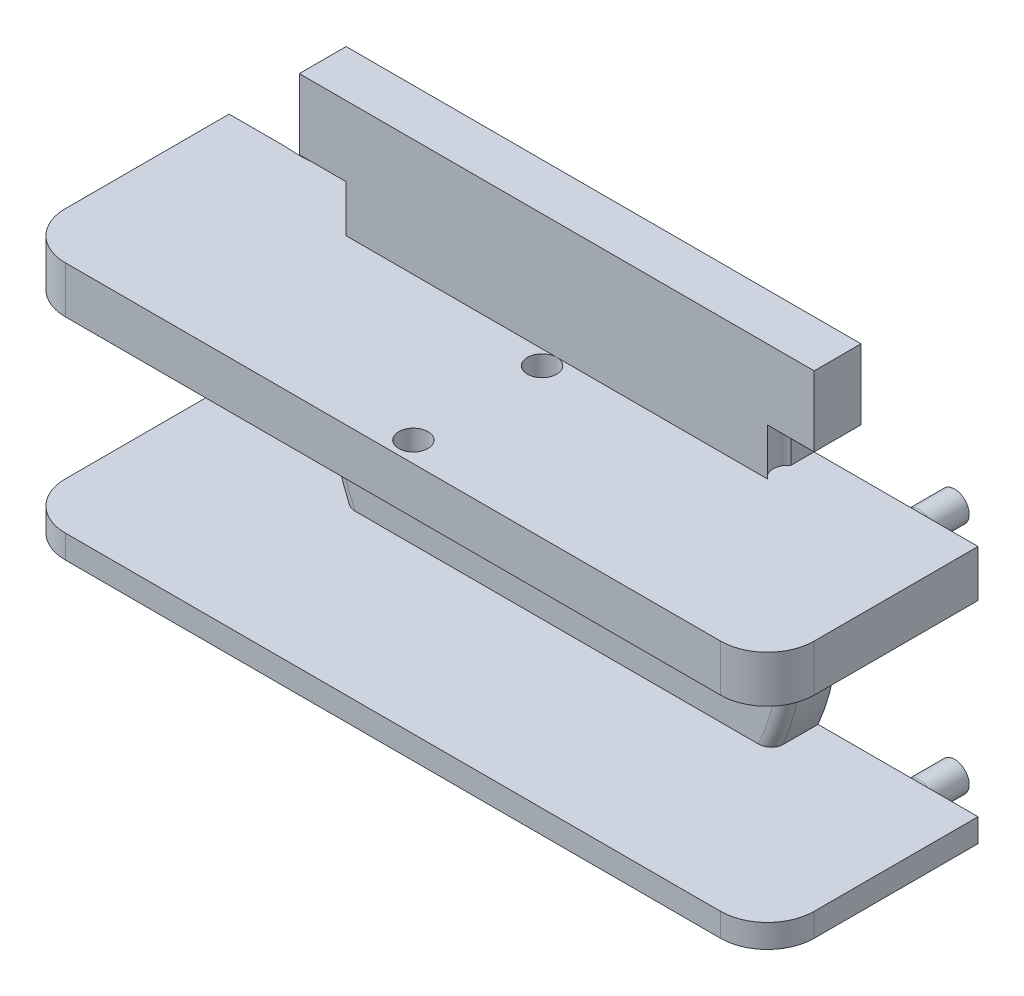
SolidWorks part; units mm, degrees
material "UNOBTANIUM"
ref_plane "Top Plane" through (0, 0, 0) normal (0, 0, 1) x (1, 0, 0)
ref_plane "Right Plane" through (0, 0, 0) normal (0, 1, 0) x (1, 0, 0)
ref_plane "Front Plane" through (0, 0, 0) normal (1, 0, 0) x (0, 0, -1)
ref_axis "x-axis" through (-17.6, 0, 0) along (1, 0, 0)
ref_axis "y-axis" through (0, -9.7375, 0) along (0, 1, 0)
ref_axis "z-axis" through (0, 0, 8.775) along (0, 0, -1)
sketch "Sketch1" plane through (0, 0, 0) normal (0, 0, 1) x (1, 0, 0)
  line L0 (-11, 6) -> (-11, 11)
  line L1 (-11, -6) -> (11, -6)
  line L2 (-11, -6) -> (-11, 6)
  line L3 (-11, 6) -> (11, 6) construction
  line L4 (11, -6) -> (11, 6)
  line L5 (-11, -6) -> (11, 6) construction
  line L6 (-11, 6) -> (11, -6) construction
  line L7 (-11, 11) -> (11, 11)
  line L8 (11, 11) -> (11, 6)
  circle A0 centre (0, 0) radius 9.25 construction
  point P0 (0, 0)
  dimension "D1" = 18.5
  dimension "D2" = 22
  dimension "D3" = 12
  dimension "D4" = 5
extrude "Boss-Extrude1" add sketch "Sketch1" along normal blind 2
sketch "Sketch2" plane through (0, 0, 2) normal (0, 0, -1) x (-1, 0, 0)
  circle A0 centre (0, 0) radius 1.575
  dimension "D1" = 3.15
extrude "Boss-Extrude2" add sketch "Sketch2" along normal blind 4 separate body
sketch "Sketch3" plane through (0, 0, 0) normal (0, 0, -1) x (-1, 0, 0)
  line L0 (11, -6) -> (-11, 6) construction
  circle A0 centre (0, 0) radius 1.8
  dimension "D1" = 3.6
extrude "Boss-Extrude3" add sketch "Sketch3" along normal blind 1
sketch "Sketch4" plane through (0, 0, 0) normal (0, 0, -1) x (-1, 0, 0)
  line L0 (11, -6) -> (-11, -6) construction
  line L1 (11, 11) -> (9, 11)
  line L2 (11, 11) -> (11, -6)
  line L3 (11, -6) -> (9, -6)
  line L4 (9, 11) -> (9, -6)
  line L5 (0, -6) -> (0, 11) construction
  line L7 (-9, 11) -> (-9, -6)
  line L8 (-11, -6) -> (-9, -6)
  line L9 (-11, 11) -> (-11, -6)
  line L10 (-11, 11) -> (-9, 11)
  line L11 (11, 11) -> (-11, 11) construction
  dimension "D1" = 2
extrude "Boss-Extrude4" add sketch "Sketch4" along normal blind 0.001
sketch "Sketch5" plane through (0, 0, 0) normal (0, 0, -1) x (-1, 0, 0)
  line L0 (-9, -6) -> (-9, 11) construction
  line L1 (9, 11) -> (-9, 11)
  line L2 (9, 11) -> (9, 9)
  line L3 (9, 9) -> (-9, 9)
  line L4 (-9, 11) -> (-9, 9)
  dimension "D1" = 2
extrude "Boss-Extrude5" add sketch "Sketch5" along normal up to surface (0.001 mm away) up to face at (-10, 2.5, -0.001)
sketch "Sketch6" plane through (11, 0, 0) normal (1, 0, 0) x (0, 0, -1)
  line L0 (-2, -6) -> (-2, 11) construction
  line L1 (0.001, -6) -> (-2, -6)
  line L2 (0.001, -6) -> (0.001, -4)
  line L3 (0.001, -4) -> (-2, -4)
  line L4 (-2, -6) -> (-2, -4)
  line L6 (0.001, 11) -> (0.001, -6) construction
  line L7 (-2, 6) -> (0.001, 6)
  line L8 (-2, 6) -> (-2, 4)
  line L9 (-2, 4) -> (0.001, 4)
  line L10 (0.001, 6) -> (0.001, 4)
  dimension "D1" = 2
extrude "Boss-Extrude6" add sketch "Sketch6" along normal blind 5
mirror "Mirror1" about plane through (0, 0, 0) normal (1, 0, 0) of "Boss-Extrude6"
sketch "Sketch7" plane through (0, 0, -0.001) normal (0, 0, -1) x (-1, 0, 0)
  line L0 (-9, -6) -> (-9, 9) construction
  line L1 (-9, 0) -> (-9, 9)
  line L2 (-9, 9) -> (0, 9)
  line L3 (-9, 0) -> (-9, -6)
  line L4 (-9, -6) -> (-6.7082, -6)
  line L5 (11, -6) -> (-11, -6) construction
  arc A0 (0, 9) -> (-6.7082, -6) centre (0, 0) ccw
  line M18 (-9, -6) -> (-9, 9)
  line M19 (-9, 9) -> (9, 9)
extrude "Boss-Extrude7" add sketch "Sketch7" against normal up to surface (0.001 mm away) contours A0 L4 M18 | A0 M19 M18 region at (8.3306, -4.5409, -0.001) region at (6.9897, 6.9897, -0.001) up to face at (1.8, 0, 0)
sketch "Sketch8" plane through (0, 0, -0.001) normal (0, 0, -1) x (-1, 0, 0)
  line L0 (-11, 4) -> (-9.1652, 4)
  line L1 (-11, 4) -> (-11, -4)
  line L2 (-11, -4) -> (-9.1652, -4)
  arc A1 (-9.1652, 4) -> (-9.1652, -4) centre (0, 0) ccw
  dimension "D1" = 10
extrude "Cut-Extrude1" cut sketch "Sketch8" against normal through all
sketch "Sketch9" plane through (0, 0, -0.001) normal (0, 0, -1) x (-1, 0, 0)
  line L0 (-16, -4) -> (-9.1652, -4) construction
  line L1 (-8.0623, 4) -> (-11, 4)
  line L2 (-8.0623, 4) -> (-8.0623, -4)
  line L3 (-8.0623, -4) -> (-11, -4)
  line L4 (-11, 4) -> (-11, -4)
  line L5 (-11, -6) -> (-11, 6) construction
  arc A0 (0, 9) -> (-6.7082, -6) centre (0, 0) ccw construction
  arc A1 (0, 9) -> (-6.7082, -6) centre (0, 0) ccw construction
extrude "Cut-Extrude2" cut sketch "Sketch9" against normal up to surface (0.001 mm away) up to face at (1.8, 0, 0)
mirror "Mirror2" about plane through (0, 0, 0) normal (1, 0, 0) of "Cut-Extrude2", "Boss-Extrude7", "Cut-Extrude1"
sketch "Sketch21" plane through (0, 0, -0.001) normal (0, 0, -1) x (-1, 0, 0)
  circle A0 centre (0, 0) radius 9.75
  circle A1 centre (0, 0) radius 9 construction
  circle A2 centre (0, 0) radius 1.8 construction
  circle A3 centre (0, 0) radius 1.8
  dimension "D1" = 0.75
extrude "Cut-Extrude11" cut sketch "Sketch21" against normal up to surface (0.001 mm away) up to face at (0, -0.7091, 0)
sketch "Sketch10" plane through (0, 0, 2) normal (0, 0, 1) x (1, 0, 0)
  line L0 (-16, -4) -> (-16, -6) construction
  line L1 (16, -6) -> (-16, -6)
  line L2 (16, -6) -> (16, -4)
  line L3 (16, -4) -> (-16, -4)
  line L4 (-16, -6) -> (-16, -4)
  line L5 (-16, -4) -> (-9.1652, -4) construction
  line L7 (-16, 6) -> (16, 6)
  line L8 (-16, 6) -> (-16, 4)
  line L9 (-16, 4) -> (16, 4)
  line L10 (16, 6) -> (16, 4)
extrude "Boss-Extrude8" add sketch "Sketch10" along normal blind 7
fillet "Fillet1" radius 0.5 2 edges at (10, 0, 2) (-10, 0, 2)
sketch "Sketch11" plane through (0, 0, -0.001) normal (0, 0, -1) x (-1, 0, 0)
  line L0 (-16, -5) -> (-13, -5) construction
  line L1 (-16, -6) -> (-16, -4) construction
  circle A0 centre (-13, -5) radius 0.625
  dimension "D1" = 1.25
  dimension "D2" = 3
extrude "Boss-Extrude9" add sketch "Sketch11" along normal blind 2
sketch "Sketch14" plane through (0, 0, -0.001) normal (0, 0, -1) x (-1, 0, 0)
  line L1 (11, 6) -> (9, 6)
  line L2 (11, 6) -> (11, 8)
  line L3 (11, 8) -> (9, 8)
  line L4 (9, 6) -> (9, 8)
  line L5 (-11, 6) -> (-9, 6)
  line L6 (-11, 6) -> (-11, 8)
  line L7 (-11, 8) -> (-9, 8)
  line L8 (-9, 6) -> (-9, 8)
  dimension "D1" = 18
  dimension "D2" = 2
extrude "Cut-Extrude5" cut sketch "Sketch14" against normal through all
sketch "Sketch12" plane through (0, 0, -0.001) normal (0, 0, -1) x (-1, 0, 0)
  line L0 (-16, -5) -> (-13, -5) construction
  line L1 (-16, -6) -> (-16, -4) construction
  line L3 (16, -5) -> (13, -5) construction
  line L4 (16, -6) -> (16, -4) construction
  circle A0 centre (13, -5) radius 0.675
  circle A1 centre (-13, -5) radius 0.625 construction
  circle A2 centre (-13, -5) radius 0.625 construction
  dimension "D1" = 1.35
  dimension "D2" = 1.25
extrude "Cut-Extrude3" cut sketch "Sketch12" against normal blind 2.5
sketch "Sketch16" plane through (0, 6, 0) normal (0, 1, 0) x (1, 0, 0)
  line L0 (-9, -2) -> (-9, 0.001) construction
  line L1 (-9, -1) -> (-9, -2)
  arc A1 (-9, -1) -> (-9, -2) centre (-9.375, -1.5) cw
  dimension "D1" = 0.25
  dimension "D2" = 1
extrude "Cut-Extrude6" cut sketch "Sketch16" along normal blind 2
mirror "Mirror3" about plane through (0, 0, 0) normal (0, 1, 0) of "Boss-Extrude9", "Cut-Extrude3"
mirror "Mirror4" about plane through (0, 0, 0) normal (1, 0, 0) of "Cut-Extrude6"
fillet "Fillet2" radius 0.5 2 edges at (12.375, 5, -0.001) (13.625, -5, -0.001)
fillet "Fillet3" radius 0.5 2 edges at (-13.675, 5, -0.001) (-13.675, -5, -0.001)
fillet "Fillet4" radius 2 4 edges at (16, -5, 9) (16, 5, 9) (-16, -5, 9) (-16, 5, 9)
sketch "Sketch17" plane through (0, -6, 0) normal (0, -1, 0) x (1, 0, 0)
  line L0 (-16, 7) -> (-16, -0.001) construction
  line L1 (-14, 9) -> (14, 9) construction
  line L2 (16, 7) -> (16, -0.001) construction
  line L3 (-16, 7) -> (-16, -0.001)
  line L4 (-14, 9) -> (14, 9)
  line L5 (16, 7) -> (16, -0.001)
  line L6 (14.5, 7) -> (14.5, -0.001)
  line L8 (-14, 7.5) -> (14, 7.5)
  line L9 (-14.5, 7) -> (-14.5, -0.001)
  line L10 (14.5, -0.001) -> (16, -0.001)
  line L11 (-14.5, -0.001) -> (-16, -0.001)
  arc A0 (-14, 9) -> (-16, 7) centre (-14, 7) ccw construction
  arc A1 (16, 7) -> (14, 9) centre (14, 7) ccw construction
  arc A2 (-14, 9) -> (-16, 7) centre (-14, 7) ccw
  arc A3 (16, 7) -> (14, 9) centre (14, 7) ccw
  arc A4 (14.5, 7) -> (14, 7.5) centre (14, 7) ccw
  arc A5 (-14, 7.5) -> (-14.5, 7) centre (-14, 7) ccw
  dimension "D1" = 1.5
extrude "Cut-Extrude7" cut sketch "Sketch17" against normal blind 1 and the other way through all
sketch "Sketch19" plane through (0, 6, 0) normal (0, 1, 0) x (1, 0, 0)
  line L0 (9, -2) -> (-9, -2) construction
  line L1 (0, -2.625) -> (0, -2) construction
  line L2 (9, -2) -> (-9, -2) construction
  circle A0 centre (0, -2.625) radius 0.625
  circle A1 centre (0, -8.125) radius 0.625
  point P4 (0, -2)
  dimension "D1" = 1.25
  dimension "D2" = 5.5
extrude "Cut-Extrude9" cut sketch "Sketch19" against normal up to surface (2 mm away) up to face at (0.0154, 4, 1.9997)
sketch "Sketch20" plane through (0, 0, -0.001) normal (0, 0, -1) x (-1, 0, 0)
  line L0 (-9, 8) -> (-11, 8) construction
  line L1 (-11, 11) -> (-9, 11)
  line L2 (-11, 11) -> (-11, 8)
  line L3 (-11, 8) -> (-9, 8)
  line L4 (-9, 11) -> (-9, 8)
  line L5 (11, 11) -> (-11, 11) construction
  line L6 (11, 8) -> (9, 8)
  line L7 (11, 8) -> (11, 11)
  line L8 (11, 11) -> (9, 11)
  line L9 (9, 8) -> (9, 11)
  dimension "D1" = 2
combine bodies "Combine2" operation type subtract main body 122 bodies to subtract 102
equation "\"D1@Sketch12\"=\"D2@Sketch12\"+.1"
